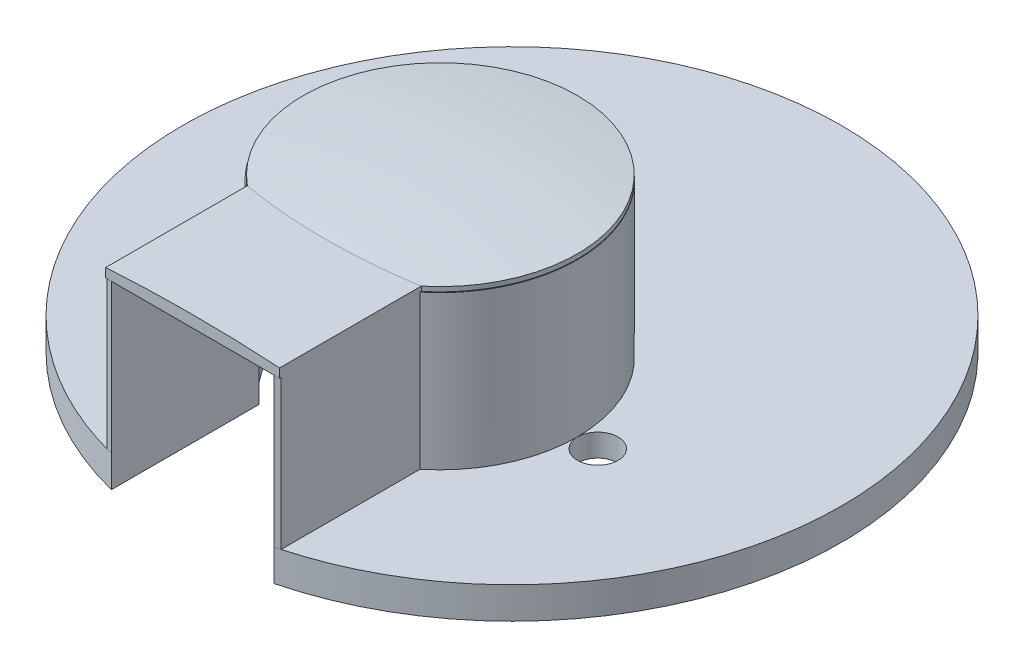
SolidWorks part; units mm, degrees
ref_plane "Front Plane" through (0, 0, 0) normal (0, 0, 1) x (1, 0, 0)
ref_plane "Top Plane" through (0, 0, 0) normal (0, 1, 0) x (1, 0, 0)
ref_plane "Right Plane" through (0, 0, 0) normal (1, 0, 0) x (0, 0, -1)
sketch "Sketch1" plane through (0, 0, 0) normal (0, 1, 0) x (1, 0, 0)
  line L0 (0, 0) -> (0, -8) construction
  line L1 (9, -19.0482) -> (-9, -19.0482) construction
  line L2 (-9, -19.0482) -> (-9, -35.373)
  line L3 (9, -19.0482) -> (9, -35.373)
  arc A0 (9, -35.373) -> (-9, -35.373) centre (0, 0) ccw
  arc A1 (9, -19.0482) -> (-9, -19.0482) centre (0, -8) ccw
  dimension "D1" = 73
  dimension "D3" = 28.5
  dimension "D2" = 8
  dimension "D4" = 18
extrude "Boss-Extrude1" add sketch "Sketch1" along normal blind 3.5
sketch "Sketch2" plane through (0, 0, 0) normal (0, 1, 0) x (1, 0, 0)
  line L0 (0, -8) -> (-14.25, -8) construction
  line L1 (0, -8) -> (14.25, -8) construction
  line L2 (-17.5, -4.25) -> (-17.5, -11.75) construction
  line L3 (-17.5, -4.25) -> (17.5, -4.25)
  line L5 (-17.5, -11.75) -> (17.5, -11.75)
  line L7 (-17.5, -4.25) -> (17.5, -11.75) construction
  line L8 (-17.5, -11.75) -> (17.5, -4.25) construction
  line L9 (17.5, -4.25) -> (17.5, -11.75) construction
  arc A1 (9, -19.0482) -> (-9, -19.0482) centre (0, -8) ccw construction
  arc A2 (-17.5, -4.25) -> (-17.5, -11.75) centre (-17.5, -8) ccw
  arc A3 (17.5, -11.75) -> (17.5, -4.25) centre (17.5, -8) ccw
  dimension "D5" = 3.75
  dimension "D1" = 7.5
  dimension "D2" = 35
extrude "Cut-Extrude1" cut sketch "Sketch2" along normal blind 1
sketch "Sketch4" plane through (0, 0, 0) normal (0, 1, 0) x (1, 0, 0)
  circle A0 centre (17.5, -8) radius 2.25
  circle A1 centre (-17.5, -8) radius 2.25
  dimension "D1" = 4.5
extrude "Cut-Extrude2" cut sketch "Sketch4" along normal blind 3
extrude "Cut-Extrude3" cut sketch "Sketch4<2>" along normal blind 8
sketch "Sketch4<2>" plane through (0, 0, 0) normal (0, 1, 0) x (1, 0, 0) same geometry as "Sketch4"
sketch "Sketch8" plane through (0, 3.5, 0) normal (0, 1, 0) x (1, 0, 0)
  line L0 (-9.6316, -19.8235) -> (-9.6316, -35.2063)
  line L1 (-9.6316, -35.2063) -> (-9, -35.373)
  line L2 (-9, -35.373) -> (-9, -19.0482)
  line L3 (9, -19.0482) -> (9, -35.373)
  line L4 (9, -19.0482) -> (9, -35.373) construction
  line L5 (9.6316, -19.8235) -> (9.6316, -35.2063)
  line L6 (9.6316, -35.2063) -> (9, -35.373)
  arc A0 (-9, -19.0482) -> (9, -19.0482) centre (0, -8) cw
  arc A1 (9, -19.0482) -> (-9, -19.0482) centre (0, -8) ccw construction
  arc A2 (-9.6316, -19.8235) -> (9.6316, -19.8235) centre (0, -8) cw
  arc A3 (9, -35.373) -> (-9, -35.373) centre (0, 0) ccw construction
  dimension "D1" = 1
extrude "Boss-Extrude4" add sketch "Sketch8" along normal blind 17
ref_plane "Plane2" through (0, 0, 0) normal (1, 0, 0) x (0, 0, -1)
sketch "Sketch10" plane through (0, 0, 0) normal (1, 0, 0) x (0, 0, -1)
  line L5 (7.25, 20.5) -> (7.25, 21)
  line L7 (-0.3432, 20.3) -> (-0.3432, 21.1) construction
  line L8 (-7.9364, 21.1) -> (-0.3432, 21.1) construction
  line L9 (-0.3432, 21.1) -> (-0.3432, 21.8) construction
  line L10 (7.25, 20.5) -> (5.75, 20.5) construction
  line L11 (6.25, 20.5) -> (-19.0482, 20.5) construction
  line L12 (-0.3432, 21.1) -> (-0.3432, 20.85) construction
  line L13 (-7.9364, 20.5) -> (-7.9364, 21.1) construction
  line L14 (-7.9364, 22.1) -> (-7.9364, 21.1)
  line L15 (5.75, 20.5) -> (7.25, 20.5)
  spline S0 degree 2 poles (-7.9364, 22.1) (-0.3072, 22.0474) (7.25, 21) knots 0 0 0 1 1 1
  spline S1 degree 2 poles (-7.9364, 21.1) (-1.0856, 20.9674) (5.75, 20.5) knots 0 0 0 1 1 1
  dimension "D2" = 0.5
  dimension "D3" = 15.237
  dimension "D8" = 13.7009
  dimension "D1" = 0.7
  dimension "D4" = 1.6
  dimension "D5" = 1.5
  dimension "D6" = 0.25
  dimension "D7" = 1
revolve "Revolve1" add sketch "Sketch10" angle 360 about L14
ref_plane "Plane3" through (0, 0, 35.373) normal (0, 0, -1) x (-1, 0, 0)
sketch "Sketch11" plane through (0, 0, 35.373) normal (0, 0, -1) x (-1, 0, 0)
  line L0 (9.6316, 21) -> (9.6316, 20)
  line L1 (9.6316, 20.5) -> (9.6316, 3.5) construction
  line L2 (9.6316, 20) -> (-9.6316, 20)
  line L3 (-9.6316, 20.5) -> (-9.6316, 3.5) construction
  line L4 (-9.6316, 20) -> (-9.6316, 21)
  line L6 (0, 20) -> (0, 21.3) construction
  spline S0 degree 2 poles (9.6316, 21) (0, 21.6) (-9.6316, 21) knots 0 0 0 1 1 1
  point P5 (9.6316, 20.5)
  dimension "D3" = 19.2756
  dimension "D1" = 1
  dimension "D2" = 1.3
extrude "Boss-Extrude5" add sketch "Sketch11" along normal blind 16
fillet "Fillet5" radius 0.3 1 edges at (0, 20, 19.373)
